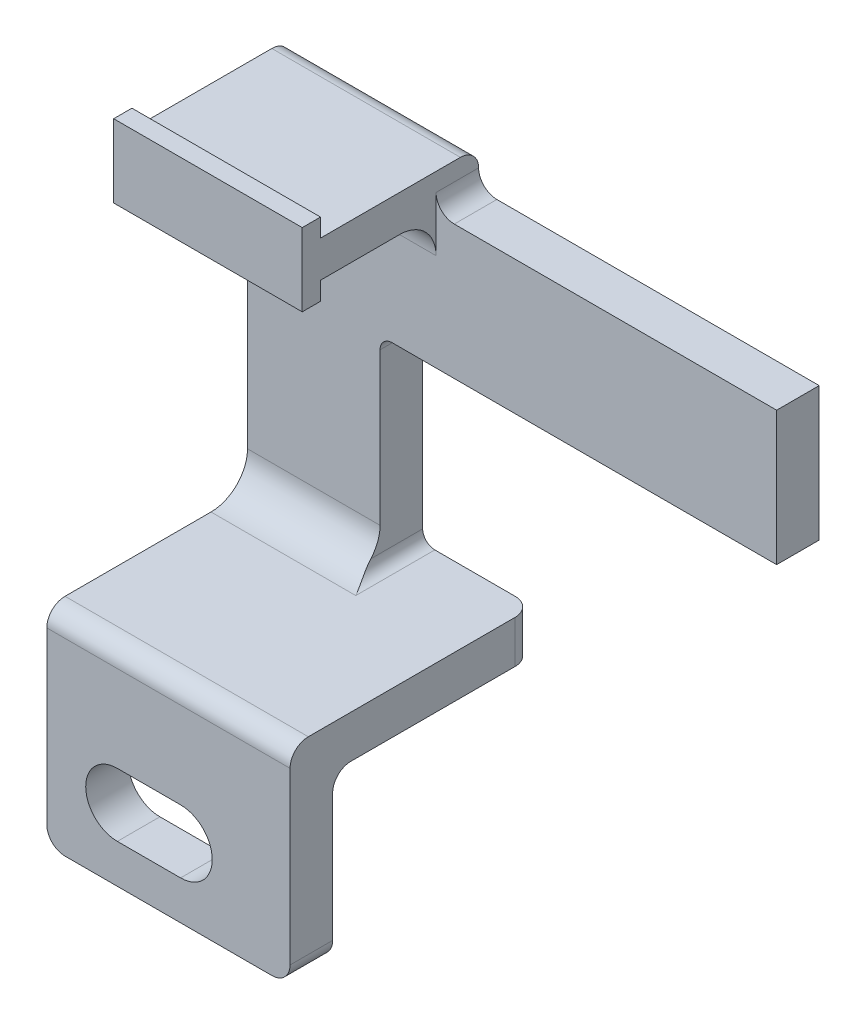
SolidWorks part; units mm, degrees
ref_plane "Front Plane" through (0, 0, 0) normal (0, 0, 1) x (1, 0, 0)
ref_plane "Top Plane" through (0, 0, 0) normal (0, 1, 0) x (1, 0, 0)
ref_plane "Right Plane" through (0, 0, 0) normal (1, 0, 0) x (0, 0, -1)
sketch "Sketch1" plane through (0, 0, 0) normal (0, 0, 1) x (1, 0, 0)
  line L0 (0, 0) -> (0, 15.5)
  line L1 (1, 16.5) -> (32.6, 16.5)
  line L2 (32.6, 16.5) -> (32.6, 27.5)
  line L3 (32.6, 27.5) -> (-10.9, 27.5)
  line L4 (-10.9, 27.5) -> (-10.9, 0)
  line L5 (-10.9, 0) -> (0, 0)
  arc A0 (0, 15.5) -> (1, 16.5) centre (1, 15.5) cw
  dimension "D5" = 1
  dimension "D1" = 11
  dimension "D2" = 43.5
  dimension "D3" = 27.5
  dimension "D4" = 10.9
extrude "Boss-Extrude1" add sketch "Sketch1" along normal blind 3.5
sketch "Sketch2" plane through (0, 0, 0) normal (0, -1, 0) x (1, 0, 0)
  line L0 (-10.9, 0) -> (9.1, 0)
  line L3 (9.1, 20) -> (-10.9, 20)
  line L4 (-10.9, 20) -> (-10.9, 0)
  line L5 (9.1, 20) -> (9.1, 0)
  dimension "D1" = 20
  dimension "D2" = 20
extrude "Boss-Extrude2" add sketch "Sketch2" along normal blind 3.5
sketch "Sketch3" plane through (0, -3.5, 0) normal (0, -1, 0) x (1, 0, 0)
  line L0 (-10.9, 20) -> (-10.9, 16.5)
  line L1 (-10.9, 20) -> (-10.9, 0) construction
  line L2 (-10.9, 16.5) -> (9.1, 16.5)
  line L3 (9.1, 0) -> (9.1, 20) construction
  line L4 (9.1, 16.5) -> (9.1, 20)
  line L5 (9.1, 20) -> (-10.9, 20)
  dimension "D1" = 3.5
extrude "Boss-Extrude3" add sketch "Sketch3" along normal blind 13.5
sketch "Sketch4" plane through (0, 27.5, 0) normal (0, 1, 0) x (1, 0, 0)
  line L0 (-10.9, 0) -> (-10.9, -3.5)
  line L2 (4.6, -3.5) -> (4.6, 0)
  line L3 (32.6, 0) -> (-10.9, 0) construction
  line L4 (4.6, 0) -> (-10.9, 0)
  line L5 (4.6, -3.5) -> (4.6, -13)
  line L6 (4.6, -13) -> (-10.9, -13)
  line L7 (-10.9, -20) -> (-10.9, -3.5) construction
  line L8 (-10.9, -13) -> (-10.9, -3.5)
  dimension "D1" = 15.5
  dimension "D2" = 13
extrude "Boss-Extrude4" add sketch "Sketch4" along normal blind 3
sketch "Sketch5" plane through (0, 0, 13) normal (0, 0, 1) x (1, 0, 0)
  line L0 (-3.15, 30.5) -> (-3.15, 27.5) construction
  line L1 (-10.9, 30.5) -> (4.6, 30.5) construction
  line L2 (-10.9, 27.5) -> (4.6, 27.5) construction
  line L3 (-10.9, 27.5) -> (-10.9, 0) construction
  line L4 (4.6, 32) -> (-10.9, 32)
  line L5 (4.6, 32) -> (4.6, 26)
  line L6 (4.6, 26) -> (-10.9, 26)
  line L7 (-10.9, 32) -> (-10.9, 26)
  line L8 (4.6, 32) -> (-10.9, 26) construction
  line L9 (4.6, 26) -> (-10.9, 32) construction
  point P6 (-3.15, 29)
  dimension "D1" = 1.5
extrude "Boss-Extrude5" add sketch "Sketch5" along normal blind 1.5
fillet "Fillet1" radius 1 1 edges at (0, 0, 1.75)
fillet "Fillet2" radius 3 2 edges at (-4.95, 0, 3.5) (-3.15, 27.5, 3.5)
fillet "Fillet3" radius 1.5 7 edges at (9.1, -1.75, 0) (-0.9, -3.5, 16.5) (9.1, -17, 18.25) (-10.9, -17, 18.25) (4.6, 27.5, 1.75) (-3.15, 30.5, 0) (-0.9, 0, 20)
sketch "Sketch6" plane through (0, 0, 16.5) normal (0, 0, -1) x (-1, 0, 0)
  line L0 (-9.1, -11.2) -> (10.9, -11.2) construction
  line L1 (-9.1, -15.5) -> (-9.1, -5) construction
  line L2 (10.9, -15.5) -> (10.9, -5) construction
  line L3 (-0.1, -8.6) -> (5.1, -8.6)
  line L4 (-0.1, -13.8) -> (5.1, -13.8)
  line L5 (9.4, -17) -> (-7.6, -17) construction
  circle A0 centre (5.1, -11.2) radius 2.6
  circle A1 centre (-0.1, -11.2) radius 2.6
  dimension "D1" = 5.2
  dimension "D2" = 5.8
  dimension "D3" = 5.8
extrude "Cut-Extrude1" cut sketch "Sketch6" against normal up to surface (3.5 mm away) contours A0 L0 | L0 A0 | A1 L4 A0 | A1 A0 L3 | A1 L0 | L0 A1 region at (-5.1, -10.0965, 16.5) region at (0.1, -12.3035, 16.5) region at (-2.5, -9.1808, 16.5) region at (-5.1, -12.3035, 16.5) region at (0.1, -10.0965, 16.5) region at (-2.5, -13.2192, 16.5) up to face at (-0.9, -11.4369, 20)
